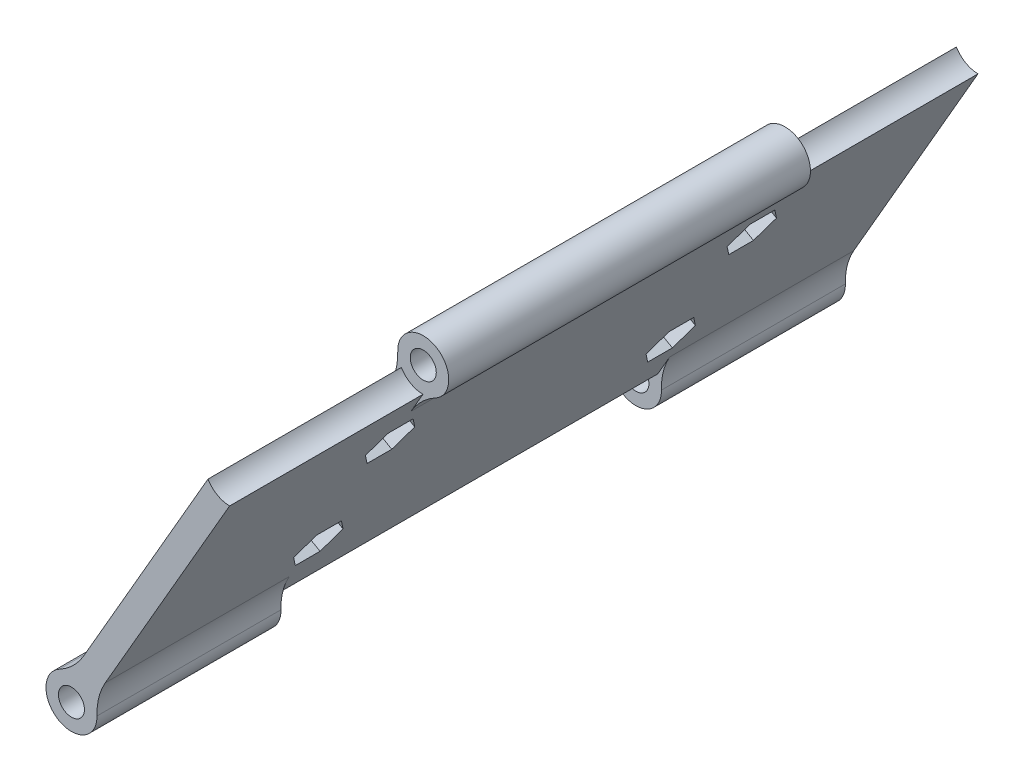
SolidWorks part; units mm, degrees
material "PLA"
ref_plane "Front Plane" through (0, 0, 0) normal (0, 0, 1) x (1, 0, 0)
ref_plane "Top Plane" through (0, 0, 0) normal (0, 1, 0) x (1, 0, 0)
ref_plane "Right Plane" through (0, 0, 0) normal (1, 0, 0) x (0, 0, -1)
sketch "Sketch2" plane through (0, 0, 0) normal (0, 0, 1) x (1, 0, 0)
  line L0 (0, 0) -> (38.1, 0)
  line L1 (0, 0) -> (0, -38.1)
  circle A0 centre (0, 0) radius 38.1
  circle A1 centre (0, -29.337) radius 1.5875
  circle A2 centre (-25.4066, 14.6685) radius 1.5875
  circle A3 centre (25.4066, 14.6685) radius 1.5875
  point P13 (0, 0)
  dimension "D1" = 76.2
  dimension "D2" = 3.175
  dimension "D3" = 8.763
  dimension "D4" = 3
extrude "Boss-Extrude1" add sketch "Sketch2" along normal blind 10 contours A1 L1 L0 A0 A3 A2 | A1 L1 A0 L0 region at (-5.4206, 5.3873, 0) region at (16.2241, -16.1243, 0)
sketch "Sketch3" plane through (0, 0, 10) normal (0, 0, 1) x (1, 0, 0)
  line L1 (0, -29.337) -> (25.4066, 14.6685)
  line L2 (1.7321, -30.337) -> (27.1386, 13.6685)
  line L3 (-1.7321, -28.337) -> (23.6745, 15.6685)
  circle A11 centre (0, -29.337) radius 1.5875
  circle A12 centre (25.4066, 14.6685) radius 1.5875
  circle A17 centre (0, -29.337) radius 2.0875
  circle A18 centre (25.4066, 14.6685) radius 2.0875
  circle A19 centre (0, -29.337) radius 4.0875
  circle A20 centre (25.4066, 14.6685) radius 4.0875
  dimension "D1" = 0.5
  dimension "D2" = 2
  dimension "D4" = 2
  dimension "D5" = 2
extrude "Boss-Extrude2" add sketch "Sketch3" along normal blind 120 separate body contours L2 A20 L3 A18 | L1 A20 L2 A18 | L3 A20 L1 A18 | A20 L1 A19 L2 | A20 L3 A19 L1 | L1 A19 L3 A17 | L2 A19 L1 A17 | L3 A19 L2 A17 region at (0.4725, -26.4041, 10) region at (2.3037, -27.4614, 10) region at (11.8338, -6.8323, 10) region at (13.5728, -7.8362, 10) region at (-1.1016, -31.245, 10) region at (23.1028, 12.7929, 10) region at (24.9341, 11.7356, 10) region at (24.355, 18.4986, 10)
delete or keep bodies "Body-Delete/Keep 2" type delete bodies bodies 101
ref_plane "Plane1" through (0, 0, 70) normal (0, 0, 1) x (1, 0, 0)
sketch "Sketch4" plane through (0, 0, 70) normal (0, 0, 1) x (1, 0, 0)
  circle A1 centre (0, -29.337) radius 4.0875
extrude "Cut-Extrude1" cut sketch "Sketch4" against normal blind 30.5 and the other way blind 30.5 contours A1
sketch "Sketch5" plane through (0, 0, 10) normal (0, 0, -1) x (-1, 0, 0)
  circle A0 centre (-25.4066, 14.6685) radius 4.0875
extrude "Cut-Extrude2" cut sketch "Sketch5" against normal offset from surface (31 mm away) 1.5 up to face at (2.0875, -29.337, 39.5) offset beyond the face yes
sketch "Sketch6" plane through (0, 0, 130) normal (0, 0, 1) x (1, 0, 0)
  circle A0 centre (25.4066, 14.6685) radius 4.0875
extrude "Cut-Extrude3" cut sketch "Sketch6" against normal offset from surface (31 mm away) 1.5 contours A0 up to face at (2.0875, -29.337, 100.5) offset beyond the face yes
fillet "Fillet1" radius 10 6 edges at (21.8921, 12.5813, 70) (0.0503, -25.2498, 24.75) (0.0503, -25.2498, 115.25) (3.5144, -27.2498, 115.25) (3.5144, -27.2498, 24.75) (25.3562, 10.5813, 70)
sketch "Sketch7" plane through (10.9712, -6.3342, 0) normal (-0.866, 0.5, 0) x (0, 0, 1)
  circle A0 centre (40.9814, 11.2661) radius 1.5
  circle A1 centre (42.4851, -11.7339) radius 1.5
  circle A2 centre (98.9814, -11.7339) radius 1.5
  circle A3 centre (98.9814, 11.2661) radius 1.5
  circle A4 centre (40.9814, 11.2661) radius 2
  circle A5 centre (42.4851, -11.7339) radius 2
  circle A6 centre (98.9814, -11.7339) radius 2
  circle A7 centre (98.9814, 11.2661) radius 2
  dimension "D1" = 0.5
extrude "Cut-Extrude4" cut sketch "Sketch7" against normal up to surface (4 mm away) contours A4 | A7 | A6 | A5 up to face at (14.7532, -7.7836, 70)
sketch "Sketch8" plane through (14.4353, -8.3342, 0) normal (0.866, -0.5, 0) x (0, 0, -1)
  line L1 (-37.0219, 11.2661) -> (-39.0016, 14.6951)
  line L2 (-39.0016, 14.6951) -> (-42.9611, 14.6951)
  line L3 (-42.9611, 14.6951) -> (-44.9408, 11.2661)
  line L4 (-44.9408, 11.2661) -> (-42.9611, 7.8371)
  line L5 (-42.9611, 7.8371) -> (-39.0016, 7.8371)
  line L6 (-39.0016, 7.8371) -> (-37.0219, 11.2661)
  line L7 (-38.5256, -11.7339) -> (-40.5053, -8.3049)
  line L8 (-40.5053, -8.3049) -> (-44.4648, -8.3049)
  line L9 (-44.4648, -8.3049) -> (-46.4445, -11.7339)
  line L10 (-46.4445, -11.7339) -> (-44.4648, -15.1629)
  line L11 (-44.4648, -15.1629) -> (-40.5053, -15.1629)
  line L12 (-40.5053, -15.1629) -> (-38.5256, -11.7339)
  line L13 (-95.0219, 11.2661) -> (-97.0016, 14.6951)
  line L14 (-97.0016, 14.6951) -> (-100.9611, 14.6951)
  line L15 (-100.9611, 14.6951) -> (-102.9408, 11.2661)
  line L16 (-102.9408, 11.2661) -> (-100.9611, 7.8371)
  line L17 (-100.9611, 7.8371) -> (-97.0016, 7.8371)
  line L18 (-97.0016, 7.8371) -> (-95.0219, 11.2661)
  line L19 (-95.0219, -11.7339) -> (-97.0016, -8.3049)
  line L20 (-97.0016, -8.3049) -> (-100.9611, -8.3049)
  line L21 (-100.9611, -8.3049) -> (-102.9408, -11.7339)
  line L22 (-102.9408, -11.7339) -> (-100.9611, -15.1629)
  line L23 (-100.9611, -15.1629) -> (-97.0016, -15.1629)
  line L24 (-97.0016, -15.1629) -> (-95.0219, -11.7339)
  circle A0 centre (-40.9814, 11.2661) radius 3.429 construction
  circle A1 centre (-42.4851, -11.7339) radius 3.429 construction
  circle A2 centre (-98.9814, 11.2661) radius 3.429 construction
  circle A3 centre (-98.9814, -11.7339) radius 3.429 construction
  dimension "D1" = 6.858
extrude "Cut-Extrude5" cut sketch "Sketch8" against normal blind 2
